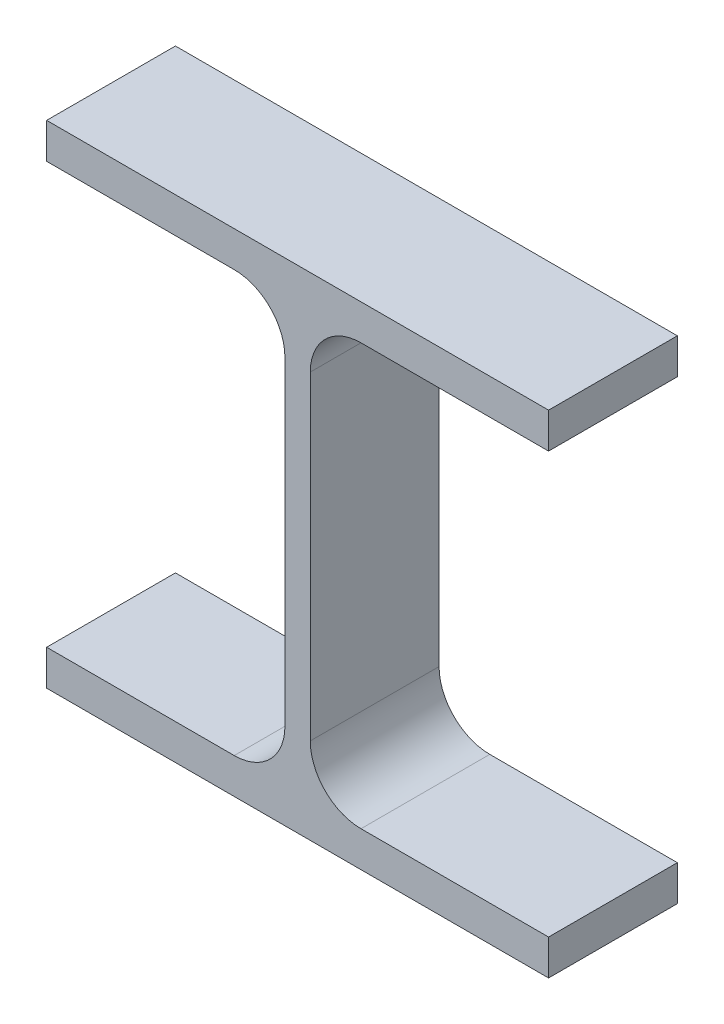
SolidWorks part; units mm, degrees
ref_plane "Front Plane" through (0, 0, 0) normal (0, 0, 1) x (1, 0, 0)
ref_plane "Top Plane" through (0, 0, 0) normal (0, 1, 0) x (1, 0, 0)
ref_plane "Right Plane" through (0, 0, 0) normal (1, 0, 0) x (0, 0, -1)
sketch "Sketch1" plane through (0, 0, 0) normal (0, 0, 1) x (1, 0, 0)
  line L0 (0, 72.9931) -> (0, -63.9253) construction
  line L1 (-49.5, 48.5) -> (49.5, 48.5)
  line L2 (-49.5, 48.5) -> (-49.5, 41.5)
  line L3 (-49.5, -48.5) -> (49.5, -48.5)
  line L4 (49.5, -41.5) -> (49.5, -48.5)
  line L5 (-42.3074, 0) -> (60.8749, 0) construction
  line L6 (-49.5, -41.5) -> (-49.5, -48.5)
  line L7 (-49.5, 41.5) -> (-12.5, 41.5)
  line L8 (49.5, -41.5) -> (12.5, -41.5)
  line L9 (-49.5, -41.5) -> (-12.5, -41.5)
  line L10 (-2.5, 31.5) -> (-2.5, -31.5)
  line L11 (2.5, 31.5) -> (2.5, -31.5)
  line L12 (49.5, 41.5) -> (12.5, 41.5)
  line L13 (49.5, 48.5) -> (49.5, 41.5)
  arc A0 (-12.5, 41.5) -> (-2.5, 31.5) centre (-12.5, 31.5) cw
  arc A1 (-12.5, -41.5) -> (-2.5, -31.5) centre (-12.5, -31.5) ccw
  arc A2 (12.5, -41.5) -> (2.5, -31.5) centre (12.5, -31.5) cw
  arc A3 (12.5, 41.5) -> (2.5, 31.5) centre (12.5, 31.5) ccw
  point P18 (0, -48.5)
  point P27 (0, 48.5)
  dimension "Radius" = 10
  dimension "Depth" = 97
  dimension "Width" = 99
  dimension "Web_thickness" = 5
  dimension "Thickness" = 7
extrude "BaseSection" add sketch "Sketch1" along normal mid plane 25.4
